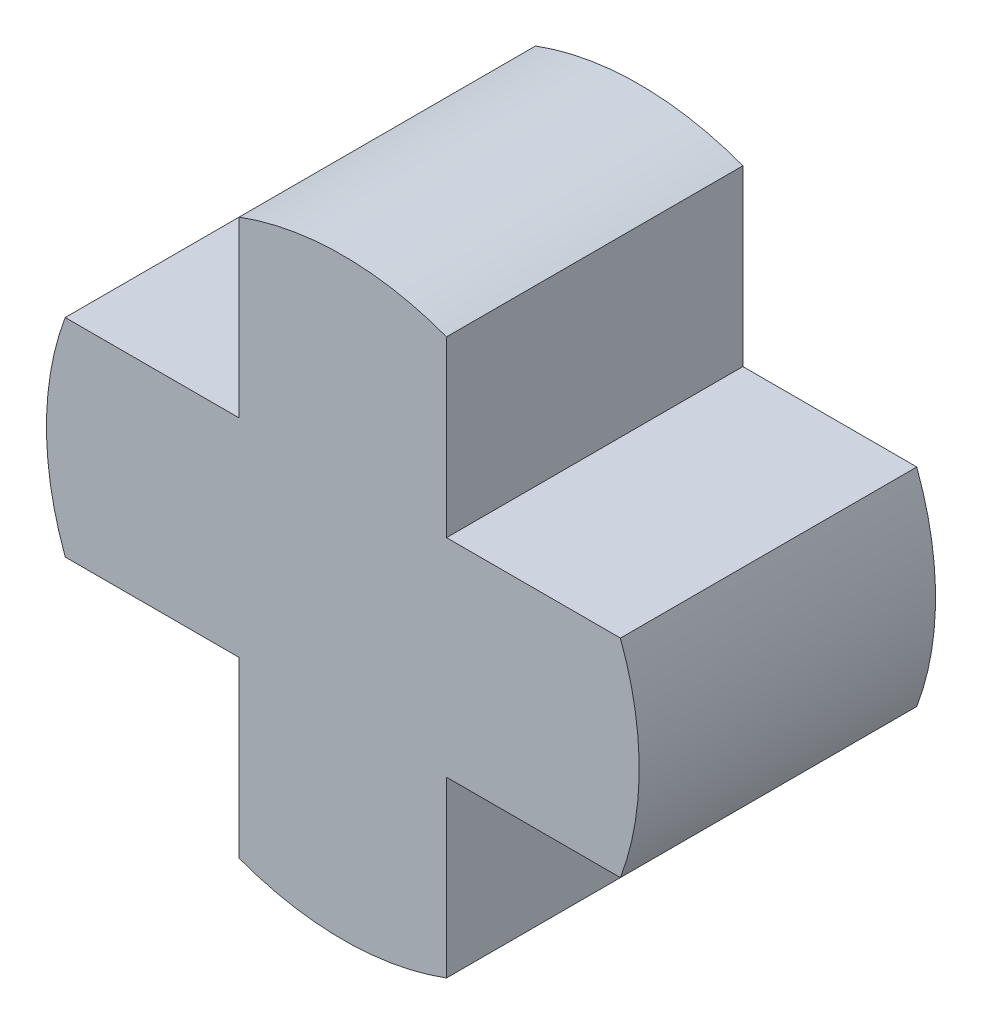
SolidWorks part; units mm, degrees
ref_plane "정면" through (0, 0, 0) normal (0, 0, 1) x (1, 0, 0)
ref_plane "윗면" through (0, 0, 0) normal (0, 1, 0) x (1, 0, 0)
ref_plane "우측면" through (0, 0, 0) normal (1, 0, 0) x (0, 0, -1)
sketch "스케치1" plane through (0, 0, 0) normal (0, 0, 1) x (1, 0, 0)
  line L1 (3.5, -10) -> (-3.5, -10)
  line L2 (3.5, -10) -> (3.5, 9.3675)
  line L4 (-3.5, -10) -> (-3.5, 9.3675)
  line L5 (3.5, -10) -> (-3.3035, 9.4386) construction
  line L6 (3.3035, 9.4386) -> (-3.5, -10) construction
  line L7 (-9.3675, -3.5) -> (9.3675, -3.5)
  line L9 (-9.3675, 3.5) -> (9.3675, 3.5)
  line L11 (-9.4386, -3.3035) -> (9.4386, 3.3035) construction
  line L12 (-9.4386, 3.3035) -> (9.4386, -3.3035) construction
  circle A0 centre (0, 0) radius 10
  dimension "D1" = 20
  dimension "D2" = 7
  dimension "D3" = 7
extrude "보스-돌출1" add sketch "스케치1" along normal blind 10 contours L2 A0 L4 L9 | L9 A0 L7 L4 | L9 L4 L7 L2 | L4 A0 L2 L7 | L7 A0 L9 L2 region at (0, -6.6488, 0) region at (0, 0, 0) region at (6.6488, 0, 0) region at (-6.6488, 0, 0) region at (0, 6.6488, 0)
